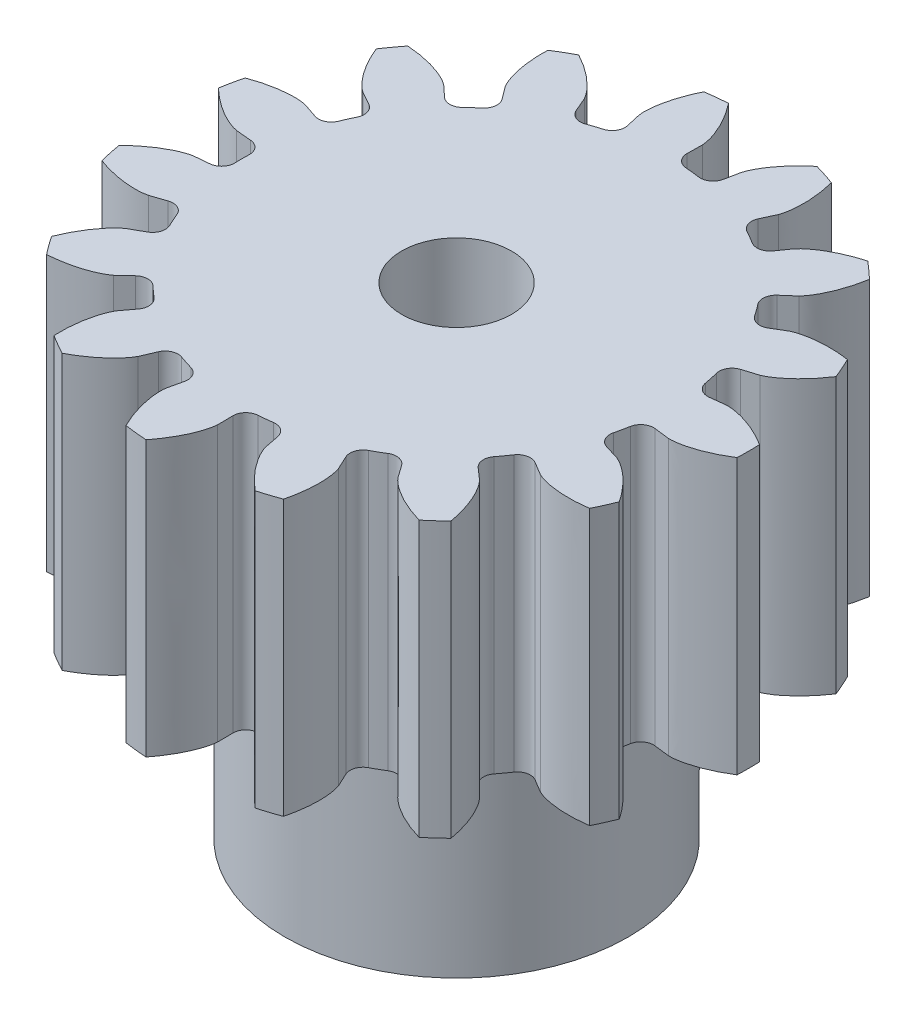
SolidWorks part; units mm, degrees
ref_plane "Front Plane" through (0, 0, 0) normal (0, 0, 1) x (1, 0, 0)
ref_plane "Top Plane" through (0, 0, 0) normal (0, 1, 0) x (1, 0, 0)
ref_plane "Right Plane" through (0, 0, 0) normal (1, 0, 0) x (0, 0, -1)
sketch "Sketch1" plane through (0, 0, 8) normal (0, -1, 0) x (1, 0, 0)
  line L0 (6.5671, -8.7894) -> (7.0134, -8.8423)
  line L1 (7.0134, -7.1577) -> (6.5671, -7.2106)
  line L2 (6.3204, -6.05) -> (6.7496, -5.9168)
  line L3 (6.0645, -4.378) -> (5.6783, -4.6078)
  line L4 (4.9809, -3.6479) -> (5.3188, -3.3516)
  line L5 (4.0669, -2.2245) -> (3.8076, -2.5915)
  line L6 (2.7801, -1.9982) -> (2.9683, -1.5902)
  line L7 (1.3662, -1.0696) -> (1.2786, -1.5104)
  line L8 (0.0986, -1.3864) -> (0.1046, -0.937)
  line L9 (-1.5707, -1.1131) -> (-1.4715, -1.5514)
  line L10 (-2.6, -1.918) -> (-2.7773, -1.5051)
  line L11 (-4.2361, -2.3474) -> (-3.9672, -2.7074)
  line L12 (-4.8489, -3.5013) -> (-5.1789, -3.1962)
  line L13 (-6.169, -4.559) -> (-5.7769, -4.7786)
  line L14 (-6.2595, -5.8625) -> (-6.685, -5.718)
  line L15 (-7.0352, -7.3657) -> (-6.5877, -7.4067)
  line L16 (-6.5877, -8.5933) -> (-7.0352, -8.6343)
  line L17 (-6.685, -10.282) -> (-6.2595, -10.1375)
  line L18 (-5.7769, -11.2214) -> (-6.169, -11.441)
  line L19 (-5.1789, -12.8038) -> (-4.8489, -12.4987)
  line L20 (-3.9672, -13.2926) -> (-4.2361, -13.6526)
  line L21 (-2.7773, -14.4949) -> (-2.6, -14.082)
  line L22 (-1.4715, -14.4486) -> (-1.5707, -14.8869)
  line L23 (0.1046, -15.063) -> (0.0986, -14.6136)
  line L24 (1.2786, -14.4896) -> (1.3662, -14.9304)
  line L25 (2.9683, -14.4098) -> (2.7801, -14.0018)
  line L26 (3.8076, -13.4085) -> (4.0669, -13.7755)
  line L27 (5.3188, -12.6484) -> (4.9809, -12.3521)
  line L28 (5.6783, -11.3922) -> (6.0645, -11.622)
  line L29 (6.7496, -10.0832) -> (6.3204, -9.95)
  arc A0 (6.0668, -9.5021) -> (6.1533, -9.0954) centre (0, -8) ccw
  arc A1 (6.1533, -9.0954) -> (6.5671, -8.7894) centre (6.5224, -9.1617) cw
  arc A2 (8.4936, -8.3269) -> (8.4936, -7.6731) centre (-0.0001, -8) ccw
  arc A3 (6.5671, -7.2106) -> (6.1533, -6.9046) centre (6.5224, -6.8383) cw
  arc A4 (6.1533, -6.9046) -> (6.0668, -6.4979) centre (0, -8) ccw
  arc A5 (6.0668, -6.4979) -> (6.3204, -6.05) centre (6.431, -6.4084) cw
  arc A6 (7.8923, -4.844) -> (7.6263, -4.2467) centre (-0.0001, -8) ccw
  arc A7 (5.6783, -4.6078) -> (5.1758, -4.4966) centre (5.486, -4.2859) cw
  arc A8 (5.1758, -4.4966) -> (4.9314, -4.1602) centre (0, -8) ccw
  arc A9 (4.9314, -4.1602) -> (4.9809, -3.6479) centre (5.2276, -3.9303) cw
  arc A10 (5.9263, -1.9068) -> (5.4404, -1.4692) centre (-0.0001, -8.0001) ccw
  arc A11 (3.8076, -2.5915) -> (3.3033, -2.6943) centre (3.501, -2.3756) cw
  arc A12 (3.3033, -2.6943) -> (2.9432, -2.4864) centre (0, -8) ccw
  arc A13 (2.9432, -2.4864) -> (2.7801, -1.9982) centre (3.1203, -2.1558) cw
  arc A14 (2.9356, -0.0231) -> (2.3137, 0.179) centre (0, -8.0001) ccw
  arc A15 (1.2786, -1.5104) -> (0.8597, -1.8094) centre (0.9107, -1.4379) cw
  arc A16 (0.8597, -1.8094) -> (0.4462, -1.7659) centre (0, -8) ccw
  arc A17 (0.4462, -1.7659) -> (0.0986, -1.3864) centre (0.4735, -1.3919) cw
  arc A18 (-0.5627, 0.4813) -> (-1.213, 0.4129) centre (0, -8.0001) ccw
  arc A19 (-1.4715, -1.5514) -> (-1.7326, -1.9949) centre (-1.8371, -1.6348) cw
  arc A20 (-1.7326, -1.9949) -> (-2.128, -2.1234) centre (0, -8) ccw
  arc A21 (-2.128, -2.1234) -> (-2.6, -1.918) centre (-2.2551, -1.7706) cw
  arc A22 (-3.9637, -0.4808) -> (-4.53, -0.8078) centre (0, -8.0001) ccw
  arc A23 (-3.9672, -2.7074) -> (-4.0252, -3.2188) centre (-4.2672, -2.9323) cw
  arc A24 (-4.0252, -3.2188) -> (-4.3343, -3.497) centre (0, -8) ccw
  arc A25 (-4.3343, -3.497) -> (-4.8489, -3.5013) centre (-4.5939, -3.2264) cw
  arc A26 (-6.6793, -2.7431) -> (-7.0637, -3.2721) centre (0.0001, -8) ccw
  arc A27 (-5.7769, -4.7786) -> (-5.6219, -5.2694) centre (-5.9595, -5.1061) cw
  arc A28 (-5.6219, -5.2694) -> (-5.7911, -5.6492) centre (0, -8) ccw
  arc A29 (-5.7911, -5.6492) -> (-6.2595, -5.8625) centre (-6.1383, -5.5076) cw
  arc A30 (-8.2401, -5.9143) -> (-8.376, -6.5539) centre (0.0001, -8) ccw
  arc A31 (-6.5877, -7.4067) -> (-6.2465, -7.7921) centre (-6.6214, -7.7802) cw
  arc A32 (-6.2465, -7.7921) -> (-6.2465, -8.2079) centre (0, -8) ccw
  arc A33 (-6.2465, -8.2079) -> (-6.5877, -8.5933) centre (-6.6214, -8.2198) cw
  arc A34 (-8.376, -9.4461) -> (-8.2401, -10.0857) centre (0.0001, -8) ccw
  arc A35 (-6.2595, -10.1375) -> (-5.7911, -10.3508) centre (-6.1383, -10.4924) cw
  arc A36 (-5.7911, -10.3508) -> (-5.6219, -10.7306) centre (0, -8) ccw
  arc A37 (-5.6219, -10.7306) -> (-5.7769, -11.2214) centre (-5.9595, -10.8939) cw
  arc A38 (-7.0637, -12.7279) -> (-6.6793, -13.2569) centre (0.0001, -8) ccw
  arc A39 (-4.8489, -12.4987) -> (-4.3343, -12.503) centre (-4.5939, -12.7736) cw
  arc A40 (-4.3343, -12.503) -> (-4.0252, -12.7812) centre (0, -8) ccw
  arc A41 (-4.0252, -12.7812) -> (-3.9672, -13.2926) centre (-4.2672, -13.0677) cw
  arc A42 (-4.53, -15.1922) -> (-3.9637, -15.5192) centre (0, -7.9999) ccw
  arc A43 (-2.6, -14.082) -> (-2.128, -13.8766) centre (-2.2551, -14.2294) cw
  arc A44 (-2.128, -13.8766) -> (-1.7326, -14.0051) centre (0, -8) ccw
  arc A45 (-1.7326, -14.0051) -> (-1.4715, -14.4486) centre (-1.8371, -14.3652) cw
  arc A46 (-1.213, -16.4129) -> (-0.5627, -16.4813) centre (0, -7.9999) ccw
  arc A47 (0.0986, -14.6136) -> (0.4462, -14.2341) centre (0.4735, -14.6081) cw
  arc A48 (0.4462, -14.2341) -> (0.8597, -14.1906) centre (0, -8) ccw
  arc A49 (0.8597, -14.1906) -> (1.2786, -14.4896) centre (0.9107, -14.5621) cw
  arc A50 (2.3137, -16.179) -> (2.9356, -15.9769) centre (0, -7.9999) ccw
  arc A51 (2.7801, -14.0018) -> (2.9432, -13.5136) centre (3.1203, -13.8442) cw
  arc A52 (2.9432, -13.5136) -> (3.3033, -13.3057) centre (0, -8) ccw
  arc A53 (3.3033, -13.3057) -> (3.8076, -13.4085) centre (3.501, -13.6244) cw
  arc A54 (5.4404, -14.5308) -> (5.9263, -14.0932) centre (-0.0001, -7.9999) ccw
  arc A55 (4.9809, -12.3521) -> (4.9314, -11.8398) centre (5.2276, -12.0697) cw
  arc A56 (4.9314, -11.8398) -> (5.1758, -11.5034) centre (0, -8) ccw
  arc A57 (5.1758, -11.5034) -> (5.6783, -11.3922) centre (5.486, -11.7141) cw
  arc A58 (7.6263, -11.7533) -> (7.8923, -11.156) centre (-0.0001, -8) ccw
  arc A59 (6.3204, -9.95) -> (6.0668, -9.5021) centre (6.431, -9.5916) cw
  spline S0 degree 3 poles (7.0134, -8.8423) (7.1365, -8.8462) (7.2601, -8.8267) (7.3807, -8.8012) (7.5494, -8.7655) (7.7147, -8.712) (7.8746, -8.6473) (8.0899, -8.5601) (8.2972, -8.4511) (8.4936, -8.3269) knots 0 0 0 0 0.00037 0.00037 0.00037 0.000887 0.000887 0.000887 0.001584 0.001584 0.001584 0.001584
  spline S1 degree 3 poles (8.4936, -7.6731) (8.3065, -7.5548) (8.1096, -7.4503) (7.9052, -7.3653) (7.7659, -7.3073) (7.6225, -7.258) (7.4762, -7.221) (7.4011, -7.202) (7.325, -7.1862) (7.2484, -7.1749) (7.1707, -7.1633) (7.0919, -7.1553) (7.0134, -7.1577) knots 0 0 0 0 0.000664 0.000664 0.000664 0.001116 0.001116 0.001116 0.001348 0.001348 0.001348 0.001583 0.001583 0.001583 0.001583
  spline S2 degree 3 poles (6.7496, -5.9168) (6.8637, -5.8703) (6.9687, -5.8023) (7.0685, -5.73) (7.208, -5.6287) (7.3374, -5.5126) (7.457, -5.3885) (7.6183, -5.2212) (7.7633, -5.0373) (7.8923, -4.844) knots 0 0 0 0 0.00037 0.00037 0.00037 0.000887 0.000887 0.000887 0.001584 0.001584 0.001584 0.001584
  spline S3 degree 3 poles (7.6263, -4.2467) (7.4073, -4.2147) (7.1849, -4.1994) (6.9636, -4.2048) (6.8128, -4.2085) (6.6617, -4.2218) (6.513, -4.2475) (6.4366, -4.2607) (6.3608, -4.2772) (6.2862, -4.298) (6.2105, -4.3191) (6.1352, -4.3437) (6.0645, -4.378) knots 0 0 0 0 0.000664 0.000664 0.000664 0.001116 0.001116 0.001116 0.001348 0.001348 0.001348 0.001583 0.001583 0.001583 0.001583
  spline S4 degree 3 poles (5.3188, -3.3516) (5.4041, -3.2627) (5.4724, -3.1579) (5.534, -3.0512) (5.6204, -2.9019) (5.6913, -2.7433) (5.7501, -2.5812) (5.8294, -2.3628) (5.8871, -2.1358) (5.9263, -1.9068) knots 0 0 0 0 0.00037 0.00037 0.00037 0.000887 0.000887 0.000887 0.001584 0.001584 0.001584 0.001584
  spline S5 degree 3 poles (5.4404, -1.4692) (5.2273, -1.5292) (5.0179, -1.6056) (4.8179, -1.7006) (4.6816, -1.7653) (4.549, -1.8389) (4.4236, -1.9229) (4.3593, -1.966) (4.2967, -2.0119) (4.237, -2.0612) (4.1764, -2.1113) (4.1176, -2.1644) (4.0669, -2.2245) knots 0 0 0 0 0.000664 0.000664 0.000664 0.001116 0.001116 0.001116 0.001348 0.001348 0.001348 0.001583 0.001583 0.001583 0.001583
  spline S6 degree 3 poles (2.9683, -1.5902) (3.01, -1.4743) (3.0298, -1.3507) (3.0427, -1.2282) (3.0609, -1.0567) (3.0612, -0.8829) (3.049, -0.7109) (3.0326, -0.4791) (2.993, -0.2483) (2.9356, -0.0231) knots 0 0 0 0 0.00037 0.00037 0.00037 0.000887 0.000887 0.000887 0.001584 0.001584 0.001584 0.001584
  spline S7 degree 3 poles (2.3137, 0.179) (2.1435, 0.0375) (1.9832, -0.1175) (1.8392, -0.2855) (1.741, -0.4001) (1.6498, -0.5213) (1.5694, -0.649) (1.5281, -0.7146) (1.4896, -0.782) (1.4551, -0.8513) (1.4202, -0.9217) (1.3881, -0.9942) (1.3662, -1.0696) knots 0 0 0 0 0.000664 0.000664 0.000664 0.001116 0.001116 0.001116 0.001348 0.001348 0.001348 0.001583 0.001583 0.001583 0.001583
  spline S8 degree 3 poles (0.1046, -0.937) (0.0956, -0.8141) (0.0633, -0.6932) (0.0253, -0.576) (-0.0278, -0.412) (-0.0983, -0.2531) (-0.1794, -0.1009) (-0.2886, 0.1041) (-0.4187, 0.2989) (-0.5627, 0.4813) knots 0 0 0 0 0.00037 0.00037 0.00037 0.000887 0.000887 0.000887 0.001584 0.001584 0.001584 0.001584
  spline S9 degree 3 poles (-1.213, 0.4129) (-1.311, 0.2145) (-1.3943, 0.0077) (-1.4576, -0.2044) (-1.5007, -0.349) (-1.5347, -0.4969) (-1.5562, -0.6462) (-1.5672, -0.7229) (-1.575, -0.8001) (-1.5783, -0.8775) (-1.5816, -0.956) (-1.5814, -1.0353) (-1.5707, -1.1131) knots 0 0 0 0 0.000664 0.000664 0.000664 0.001116 0.001116 0.001116 0.001348 0.001348 0.001348 0.001583 0.001583 0.001583 0.001583
  spline S10 degree 3 poles (-2.7773, -1.5051) (-2.8355, -1.3965) (-2.9141, -1.2992) (-2.9965, -1.2076) (-3.1118, -1.0793) (-3.2407, -0.9628) (-3.3767, -0.8568) (-3.5599, -0.7139) (-3.758, -0.5889) (-3.9637, -0.4808) knots 0 0 0 0 0.00037 0.00037 0.00037 0.000887 0.000887 0.000887 0.001584 0.001584 0.001584 0.001584
  spline S11 degree 3 poles (-4.53, -0.8078) (-4.5388, -1.0289) (-4.5308, -1.2517) (-4.5023, -1.4712) (-4.4828, -1.6209) (-4.4538, -1.7698) (-4.4127, -1.915) (-4.3916, -1.9895) (-4.3673, -2.0632) (-4.3388, -2.1352) (-4.3099, -2.2083) (-4.2775, -2.2806) (-4.2361, -2.3474) knots 0 0 0 0 0.000664 0.000664 0.000664 0.001116 0.001116 0.001116 0.001348 0.001348 0.001348 0.001583 0.001583 0.001583 0.001583
  spline S12 degree 3 poles (-5.1789, -3.1962) (-5.2762, -3.1207) (-5.3876, -3.0637) (-5.5001, -3.0136) (-5.6576, -2.9433) (-5.8228, -2.8893) (-5.9902, -2.8478) (-6.2157, -2.7918) (-6.4475, -2.7581) (-6.6793, -2.7431) knots 0 0 0 0 0.00037 0.00037 0.00037 0.000887 0.000887 0.000887 0.001584 0.001584 0.001584 0.001584
  spline S13 degree 3 poles (-7.0637, -3.2721) (-6.9818, -3.4777) (-6.8839, -3.678) (-6.7685, -3.8669) (-6.6899, -3.9957) (-6.6028, -4.1199) (-6.5062, -4.2358) (-6.4566, -4.2953) (-6.4044, -4.3528) (-6.3491, -4.407) (-6.293, -4.462) (-6.234, -4.5149) (-6.169, -4.559) knots 0 0 0 0 0.000664 0.000664 0.000664 0.001116 0.001116 0.001116 0.001348 0.001348 0.001348 0.001583 0.001583 0.001583 0.001583
  spline S14 degree 3 poles (-6.685, -5.718) (-6.8046, -5.6886) (-6.9296, -5.6819) (-7.0528, -5.6818) (-7.2252, -5.6817) (-7.3981, -5.6995) (-7.5679, -5.7296) (-7.7967, -5.7702) (-8.0221, -5.8337) (-8.2401, -5.9143) knots 0 0 0 0 0.00037 0.00037 0.00037 0.000887 0.000887 0.000887 0.001584 0.001584 0.001584 0.001584
  spline S15 degree 3 poles (-8.376, -6.5539) (-8.2176, -6.7084) (-8.0467, -6.8516) (-7.8644, -6.9773) (-7.7402, -7.0629) (-7.6102, -7.141) (-7.4748, -7.2076) (-7.4053, -7.2418) (-7.3342, -7.273) (-7.2616, -7.3001) (-7.188, -7.3275) (-7.1126, -7.3518) (-7.0352, -7.3657) knots 0 0 0 0 0.000664 0.000664 0.000664 0.001116 0.001116 0.001116 0.001348 0.001348 0.001348 0.001583 0.001583 0.001583 0.001583
  spline S16 degree 3 poles (-7.0352, -8.6343) (-7.1565, -8.6561) (-7.2734, -8.7008) (-7.386, -8.7508) (-7.5435, -8.8209) (-7.6942, -8.9075) (-7.8371, -9.0041) (-8.0296, -9.1341) (-8.2097, -9.2839) (-8.376, -9.4461) knots 0 0 0 0 0.00037 0.00037 0.00037 0.000887 0.000887 0.000887 0.001584 0.001584 0.001584 0.001584
  spline S17 degree 3 poles (-8.2401, -10.0857) (-8.0324, -10.1625) (-7.8181, -10.2237) (-7.6005, -10.2644) (-7.4522, -10.2922) (-7.3016, -10.3106) (-7.1508, -10.3164) (-7.0734, -10.3193) (-6.9958, -10.3189) (-6.9185, -10.3141) (-6.8401, -10.3093) (-6.7613, -10.3008) (-6.685, -10.282) knots 0 0 0 0 0.000664 0.000664 0.000664 0.001116 0.001116 0.001116 0.001348 0.001348 0.001348 0.001583 0.001583 0.001583 0.001583
  spline S18 degree 3 poles (-6.169, -11.441) (-6.2709, -11.5102) (-6.3595, -11.5986) (-6.442, -11.6901) (-6.5575, -11.8181) (-6.6599, -11.9586) (-6.7511, -12.1049) (-6.8741, -12.302) (-6.9777, -12.5121) (-7.0637, -12.7279) knots 0 0 0 0 0.00037 0.00037 0.00037 0.000887 0.000887 0.000887 0.001584 0.001584 0.001584 0.001584
  spline S19 degree 3 poles (-6.6793, -13.2569) (-6.4584, -13.2426) (-6.2377, -13.2114) (-6.0224, -13.1601) (-5.8756, -13.1251) (-5.7306, -13.0807) (-5.5905, -13.0246) (-5.5186, -12.9958) (-5.4478, -12.9639) (-5.3791, -12.9281) (-5.3095, -12.8917) (-5.2409, -12.8519) (-5.1789, -12.8038) knots 0 0 0 0 0.000664 0.000664 0.000664 0.001116 0.001116 0.001116 0.001348 0.001348 0.001348 0.001583 0.001583 0.001583 0.001583
  spline S20 degree 3 poles (-4.2361, -13.6526) (-4.301, -13.7573) (-4.3461, -13.8741) (-4.3842, -13.9912) (-4.4376, -14.1552) (-4.474, -14.3251) (-4.4979, -14.4959) (-4.53, -14.726) (-4.5392, -14.9601) (-4.53, -15.1922) knots 0 0 0 0 0.00037 0.00037 0.00037 0.000887 0.000887 0.000887 0.001584 0.001584 0.001584 0.001584
  spline S21 degree 3 poles (-3.9637, -15.5192) (-3.7677, -15.4162) (-3.5788, -15.2979) (-3.4029, -15.1635) (-3.2831, -15.0718) (-3.1686, -14.9722) (-3.0635, -14.864) (-3.0095, -14.8085) (-2.9578, -14.7506) (-2.9096, -14.6899) (-2.8608, -14.6284) (-2.8144, -14.5641) (-2.7773, -14.4949) knots 0 0 0 0 0.000664 0.000664 0.000664 0.001116 0.001116 0.001116 0.001348 0.001348 0.001348 0.001583 0.001583 0.001583 0.001583
  spline S22 degree 3 poles (-1.5707, -14.8869) (-1.5875, -15.009) (-1.5811, -15.134) (-1.5683, -15.2565) (-1.5504, -15.428) (-1.5145, -15.598) (-1.4669, -15.7638) (-1.4026, -15.9871) (-1.3159, -16.2046) (-1.213, -16.4129) knots 0 0 0 0 0.00037 0.00037 0.00037 0.000887 0.000887 0.000887 0.001584 0.001584 0.001584 0.001584
  spline S23 degree 3 poles (-0.5627, -16.4813) (-0.4255, -16.3075) (-0.301, -16.1226) (-0.1951, -15.9283) (-0.1229, -15.7958) (-0.0588, -15.6583) (-0.0067, -15.5166) (0.02, -15.4439) (0.0436, -15.37) (0.0629, -15.295) (0.0825, -15.2189) (0.0988, -15.1413) (0.1046, -15.063) knots 0 0 0 0 0.000664 0.000664 0.000664 0.001116 0.001116 0.001116 0.001348 0.001348 0.001348 0.001583 0.001583 0.001583 0.001583
  spline S24 degree 3 poles (1.3662, -14.9304) (1.4006, -15.0487) (1.4572, -15.1603) (1.5188, -15.267) (1.6049, -15.4164) (1.7068, -15.5572) (1.8177, -15.6892) (1.9673, -15.867) (2.135, -16.0305) (2.3137, -16.179) knots 0 0 0 0 0.00037 0.00037 0.00037 0.000887 0.000887 0.000887 0.001584 0.001584 0.001584 0.001584
  spline S25 degree 3 poles (2.9356, -15.9769) (2.9902, -15.7624) (3.0288, -15.5428) (3.0465, -15.3222) (3.0586, -15.1718) (3.0612, -15.0201) (3.0511, -14.8695) (3.046, -14.7922) (3.0375, -14.7151) (3.0246, -14.6387) (3.0116, -14.5612) (2.9949, -14.4838) (2.9683, -14.4098) knots 0 0 0 0 0.000664 0.000664 0.000664 0.001116 0.001116 0.001116 0.001348 0.001348 0.001348 0.001583 0.001583 0.001583 0.001583
  spline S26 degree 3 poles (4.0669, -13.7755) (4.1464, -13.8696) (4.2436, -13.9485) (4.3432, -14.021) (4.4827, -14.1225) (4.633, -14.2096) (4.7881, -14.2851) (4.997, -14.3867) (5.2167, -14.4678) (5.4404, -14.5308) knots 0 0 0 0 0.00037 0.00037 0.00037 0.000887 0.000887 0.000887 0.001584 0.001584 0.001584 0.001584
  spline S27 degree 3 poles (5.9263, -14.0932) (5.889, -13.8751) (5.8349, -13.6588) (5.7613, -13.45) (5.7112, -13.3077) (5.6518, -13.1681) (5.5814, -13.0346) (5.5453, -12.9661) (5.5062, -12.8991) (5.4633, -12.8345) (5.4199, -12.7691) (5.3732, -12.7051) (5.3188, -12.6484) knots 0 0 0 0 0.000664 0.000664 0.000664 0.001116 0.001116 0.001116 0.001348 0.001348 0.001348 0.001583 0.001583 0.001583 0.001583
  spline S28 degree 3 poles (6.0645, -11.622) (6.1754, -11.6757) (6.2962, -11.7082) (6.4167, -11.7339) (6.5853, -11.7699) (6.7581, -11.7883) (6.9305, -11.7942) (7.1627, -11.8021) (7.3964, -11.7868) (7.6263, -11.7533) knots 0 0 0 0 0.00037 0.00037 0.00037 0.000887 0.000887 0.000887 0.001584 0.001584 0.001584 0.001584
  spline S29 degree 3 poles (7.8923, -11.156) (7.7694, -10.9719) (7.632, -10.7963) (7.4799, -10.6355) (7.3763, -10.5259) (7.2653, -10.4225) (7.1467, -10.3292) (7.0858, -10.2813) (7.0228, -10.236) (6.9574, -10.1944) (6.8911, -10.1523) (6.8224, -10.1128) (6.7496, -10.0832) knots 0 0 0 0 0.000664 0.000664 0.000664 0.001116 0.001116 0.001116 0.001348 0.001348 0.001348 0.001583 0.001583 0.001583 0.001583
extrude "Boss-Extrude1" add sketch "Sketch1" against normal blind 4 and the other way blind 4
sketch "Sketch2" plane through (0, -4, 0) normal (0, -1, 0) x (-1, 0, 0)
  circle A0 centre (0, 0) radius 5
  dimension "D1" = 10
extrude "Boss-Extrude2" add sketch "Sketch2" along normal blind 6
sketch "Sketch3" plane through (0, -10, 0) normal (0, -1, 0) x (-1, 0, 0)
  circle A0 centre (0, 0) radius 1.6
  dimension "D1" = 3.2
extrude "Cut-Extrude1" cut sketch "Sketch3" against normal up to next
